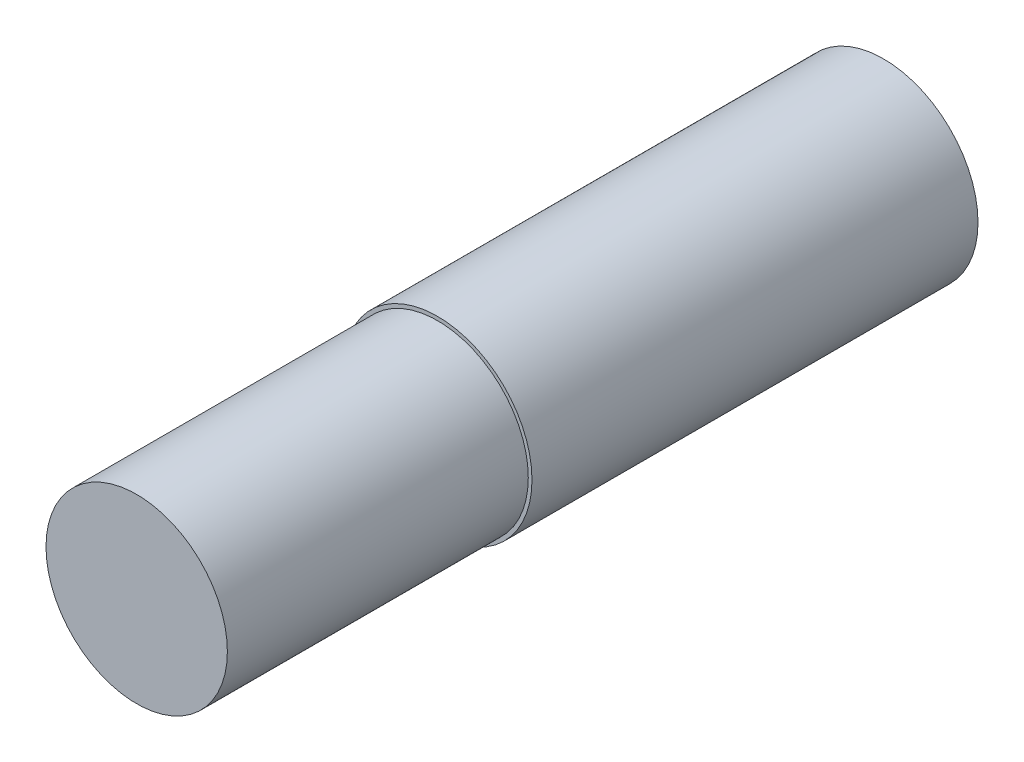
SolidWorks part; units mm, degrees
ref_plane "Front Plane" through (0, 0, 0) normal (0, 0, 1) x (1, 0, 0)
ref_plane "Top Plane" through (0, 0, 0) normal (0, 1, 0) x (1, 0, 0)
ref_plane "Right Plane" through (0, 0, 0) normal (1, 0, 0) x (0, 0, -1)
sketch "Sketch1" plane through (0, 0, 0) normal (0, 0, 1) x (1, 0, 0)
  circle A0 centre (0, 0) radius 3.175
  dimension "D1" = 6.35
extrude "Boss-Extrude1" add sketch "Sketch1" along normal blind 15
sketch "Sketch2" plane through (0, 0, 15) normal (0, 0, 1) x (1, 0, 0)
  circle A0 centre (0, 0) radius 3.05
  dimension "D1" = 6.1
extrude "Boss-Extrude2" add sketch "Sketch2" along normal blind 10.12
